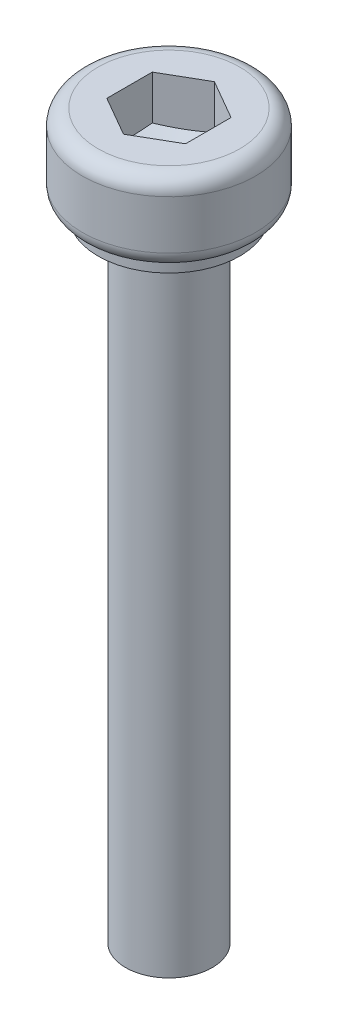
SolidWorks part; units mm, degrees
ref_plane "Front Plane" through (0, 0, 0) normal (0, 0, 1) x (1, 0, 0)
ref_plane "Top Plane" through (0, 0, 0) normal (0, 1, 0) x (1, 0, 0)
ref_plane "Right Plane" through (0, 0, 0) normal (1, 0, 0) x (0, 0, -1)
sketch "Sketch1" plane through (0, 0, 0) normal (0, 0, 1) x (1, 0, 0)
  line L0 (0, 4.0942) -> (0, -5.2249) construction
  line L1 (0, 11.475) -> (2.25, 11.475)
  line L2 (2.75, 10.975) -> (2.75, 9.425)
  line L3 (2.25, 8.525) -> (1.375, 8.525)
  line L4 (1.375, 8.525) -> (1.375, -11.475)
  line L5 (1.375, -11.475) -> (0, -11.475)
  line L6 (0, -11.475) -> (0, 11.475)
  line L7 (2.25, 8.525) -> (2.25, 8.925)
  line L8 (2.75, 8.525) -> (2.25, 8.525) construction
  line L9 (2.75, 9.425) -> (2.75, 8.525) construction
  line L10 (2.75, 11.475) -> (2.75, 10.975) construction
  line L11 (2.25, 11.475) -> (2.75, 11.475) construction
  arc A0 (2.25, 8.925) -> (2.75, 9.425) centre (2.25, 9.425) ccw
  arc A1 (2.25, 11.475) -> (2.75, 10.975) centre (2.25, 10.975) cw
  point P5 (0, 0)
  point P17 (0, 0)
  point P18 (0, 0)
  point P19 (2.25, 2.4541)
  dimension "D5" = 0.5
  dimension "D1" = 20
  dimension "D2" = 1.375
  dimension "D3" = 2.95
  dimension "D4" = 2.75
  dimension "D6" = 0.4
revolve "Revolve1" add sketch "Sketch1" angle 360 about L0
sketch "Sketch2" plane through (0, 11.475, 0) normal (0, 1, 0) x (1, 0, 0)
  line L1 (0, 1.4434) -> (-1.25, 0.7217)
  line L2 (-1.25, 0.7217) -> (-1.25, -0.7217)
  line L3 (-1.25, -0.7217) -> (0, -1.4434)
  line L4 (0, -1.4434) -> (1.25, -0.7217)
  line L5 (1.25, -0.7217) -> (1.25, 0.7217)
  line L6 (1.25, 0.7217) -> (0, 1.4434)
  circle A0 centre (0, 0) radius 1.25 construction
  dimension "D1" = 2.5
extrude "Boss-Extrude1" add sketch "Sketch2" against normal blind 2 separate body
sketch "Sketch3" plane through (0, 0, 0) normal (1, 0, 0) x (0, 0, -1)
  line L0 (0, 9.875) -> (0.4, 9.875)
  line L1 (0.4, 9.875) -> (1.4434, 10.075)
  line L2 (1.4434, 9.475) -> (1.4434, 11.475) construction
  line L3 (1.4434, 10.075) -> (1.4434, 9.475)
  line L4 (1.4434, 9.475) -> (0, 9.475)
  line L5 (-0.7217, 9.475) -> (0.7217, 9.475) construction
  line L6 (0, 9.475) -> (0, 9.875)
  line L7 (-0.7217, 11.475) -> (0.7217, 11.475) construction
  dimension "D1" = 1.6
  dimension "D2" = 1.4
  dimension "D3" = 0.4
revolve "Cut-Revolve1" cut sketch "Sketch3" angle 360 about L6
combine bodies "Combine1" operation type subtract main body 101 bodies to subtract 104
equation "\"Length\" = 20mm"
equation "\"D1@Sketch1\"=\"Length\""
equation "\"ThreadDiam\" = 2.75mm"
equation "\"D2@Sketch1\"=\"ThreadDiam\"/2"
equation "\"HeadHeight\" = 2.95mm"
equation "\"D3@Sketch1\"=\"HeadHeight\""
equation "\"HeadDiam\" = 5.5mm"
equation "\"D4@Sketch1\"=\"HeadDiam\"/2"
equation "\"HexSize\" = 2.5mm"
equation "\"D1@Sketch2\"=\"HexSize\""
